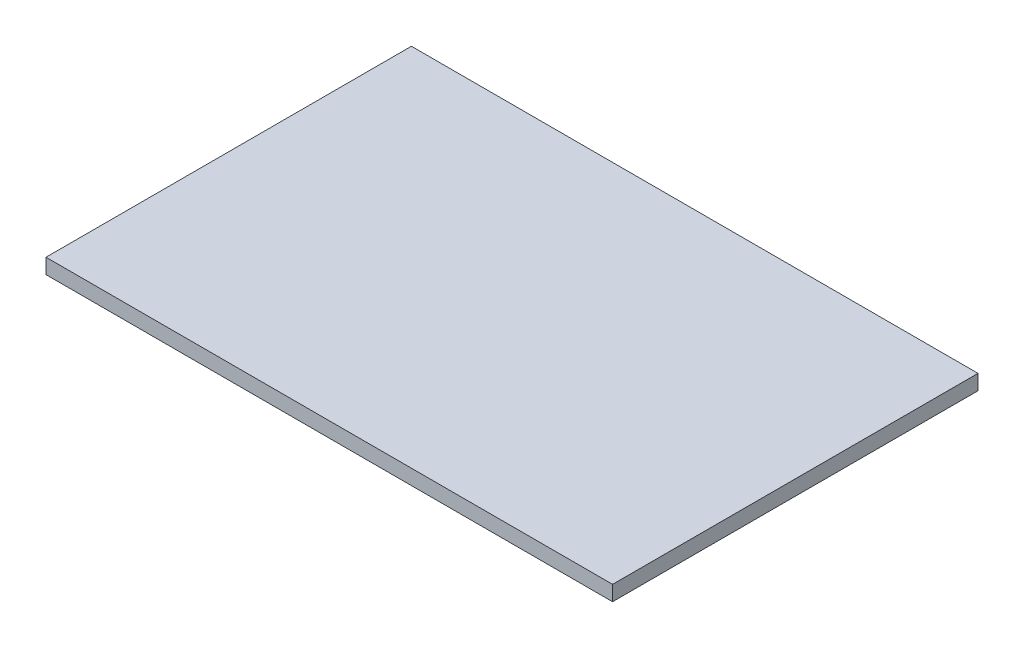
SolidWorks part; units mm, degrees
ref_plane "Front Plane" through (0, 0, 0) normal (0, 0, 1) x (1, 0, 0)
ref_plane "Top Plane" through (0, 0, 0) normal (0, 1, 0) x (1, 0, 0)
ref_plane "Right Plane" through (0, 0, 0) normal (1, 0, 0) x (0, 0, -1)
sketch "Sketch1" plane through (0, 0, 0) normal (0, 1, 0) x (1, 0, 0)
  line L1 (-169, -109) -> (169, -109)
  line L2 (-169, -109) -> (-169, 109)
  line L3 (-169, 109) -> (169, 109)
  line L4 (169, -109) -> (169, 109)
  line L5 (-169, -109) -> (169, 109) construction
  line L6 (-169, 109) -> (169, -109) construction
  point P0 (0, 0)
  dimension "D1" = 338
  dimension "D2" = 218
extrude "Boss-Extrude1" add sketch "Sketch1" along normal blind 9
sketch "Sketch2" plane through (0, 9, 0) normal (0, 1, 0) x (1, 0, 0)
  line L14 (-160, -100) -> (160, -100)
  line L15 (160, -100) -> (160, 100)
  line L16 (160, 100) -> (-160, 100)
  line L17 (-160, 100) -> (-160, -100)
  line L18 (-160, -100) -> (160, -100)
  line L19 (160, -100) -> (160, 100)
  line L20 (160, 100) -> (-160, 100)
  line L21 (-160, 100) -> (-160, -100)
  dimension "D1" = 9
equation "\"PCLength\"= 320mm'Length across I/O from PS to GPU"
equation "\"PCWidth\"= 242mm'Distance of longest part parallel to GPU(ussually GPU)"
equation "\"PCHeight\"= 172mm'Tallest point with mobo laying flat"
equation "\"WallThickness\"= 9mm'Thickness of each outer tank wall"
equation "\"ThermoBarrierThickness\"= 3mm'Thickness of barrier between hot side and cold side"
equation "\"HotSideGap\"= 25mm'Space in the hot side for a pump"
equation "\"PCClearance\"= 30mm'Clearance from top of tank to top of PC"
equation "\"RadiatorHeight\"= 275mm'Final Height from ground of radiators"
equation "\"AirflowGap\"= 36mm'Distance between radiators and tank for airflow"
equation "\"VolumeSubtraction\"= 230mm"
equation "\"D1@Sketch1\"=\"PCLength\" + (2 * \"WallThickness\")"
equation "\"D1@Boss-Extrude1\"=\"WallThickness\""
